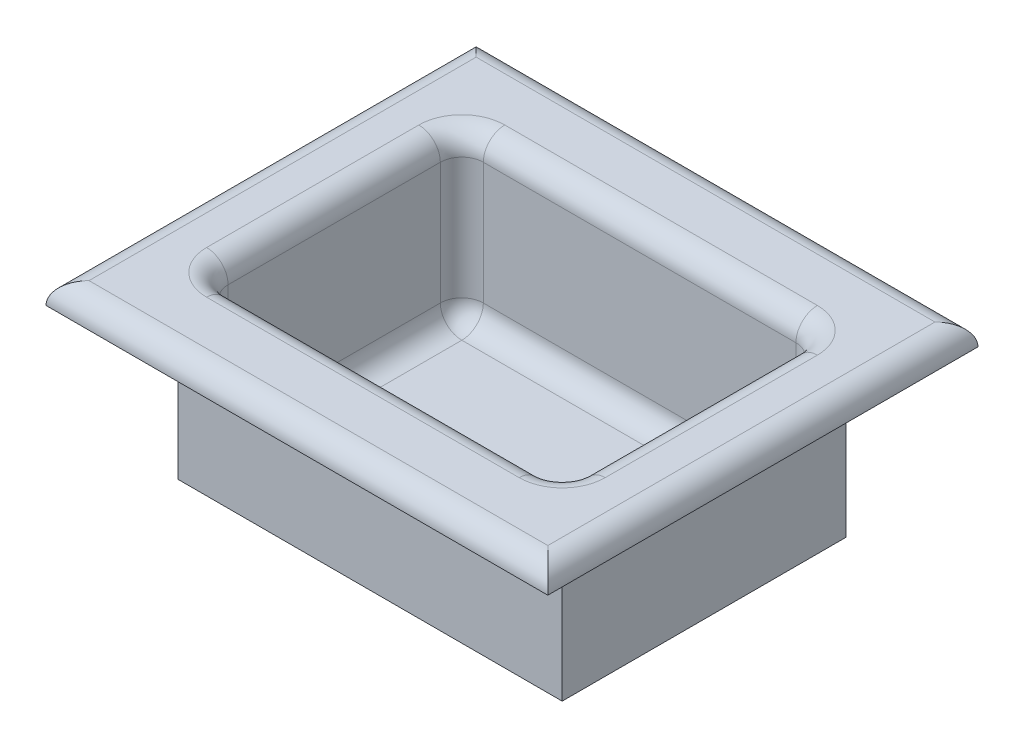
SolidWorks part; units mm, degrees
ref_plane "Спереди" through (0, 0, 0) normal (0, 0, 1) x (1, 0, 0)
ref_plane "Сверху" through (0, 0, 0) normal (0, 1, 0) x (1, 0, 0)
ref_plane "Справа" through (0, 0, 0) normal (1, 0, 0) x (0, 0, -1)
sketch "Sketch1" plane through (0, 0, 0) normal (0, 1, 0) x (1, 0, 0)
  line L1 (26.8, -19.8) -> (-26.8, -19.8)
  line L2 (26.8, -19.8) -> (26.8, 19.8)
  line L3 (26.8, 19.8) -> (-26.8, 19.8)
  line L4 (-26.8, -19.8) -> (-26.8, 19.8)
  line L5 (26.8, -19.8) -> (-26.8, 19.8) construction
  line L6 (26.8, 19.8) -> (-26.8, -19.8) construction
  point P0 (0, 0)
  dimension "D1" = 53.6
  dimension "D2" = 39.6
extrude "Boss-Extrude1" add sketch "Sketch1" along normal blind 2
sketch "Sketch2" plane through (0, 2, 0) normal (0, 1, 0) x (1, 0, 0)
  line L1 (26.8, -19.8) -> (-26.8, -19.8)
  line L2 (26.8, -19.8) -> (26.8, 19.8)
  line L3 (26.8, 19.8) -> (-26.8, 19.8)
  line L4 (-26.8, -19.8) -> (-26.8, 19.8)
  line L5 (26.8, -19.8) -> (-26.8, 19.8) construction
  line L6 (26.8, 19.8) -> (-26.8, -19.8) construction
  line L7 (24.8, -17.8) -> (-24.8, -17.8)
  line L8 (24.8, -17.8) -> (24.8, 17.8)
  line L9 (24.8, 17.8) -> (-24.8, 17.8)
  line L10 (-24.8, -17.8) -> (-24.8, 17.8)
  line L11 (24.8, -17.8) -> (-24.8, 17.8) construction
  line L12 (24.8, 17.8) -> (-24.8, -17.8) construction
  point P0 (0, 0)
  point P7 (0, 0)
  dimension "D1" = 2
  dimension "D2" = 2
extrude "Boss-Extrude2" add sketch "Sketch2" along normal blind 20
sketch "Sketch3" plane through (0, 22, 0) normal (0, 1, 0) x (1, 0, 0)
  line L1 (24.8, -17.8) -> (-24.8, -17.8)
  line L2 (24.8, -17.8) -> (24.8, 17.8)
  line L3 (24.8, 17.8) -> (-24.8, 17.8)
  line L4 (-24.8, -17.8) -> (-24.8, 17.8)
  line L5 (24.8, -17.8) -> (-24.8, 17.8) construction
  line L6 (24.8, 17.8) -> (-24.8, -17.8) construction
  line L7 (35, -30) -> (-35, -30)
  line L8 (35, -30) -> (35, 30)
  line L9 (35, 30) -> (-35, 30)
  line L10 (-35, -30) -> (-35, 30)
  line L11 (35, -30) -> (-35, 30) construction
  line L12 (35, 30) -> (-35, -30) construction
  point P0 (0, 0)
  point P7 (0, 0)
  dimension "D1" = 70
  dimension "D2" = 60
extrude "Boss-Extrude3" add sketch "Sketch3" along normal blind 3
fillet "Fillet1" radius 3 16 edges at (24.8, 13.5, 17.8) (0, 25, 17.8) (-24.8, 13.5, 17.8) (0, 2, 17.8) (24.8, 13.5, -17.8) (-24.8, 13.5, -17.8) (24.8, 2, 0) (-24.8, 2, 0) (0, 2, -17.8) (24.8, 25, 0) (0, 25, -17.8) (-24.8, 25, 0) (0, 25, 30) (0, 25, -30) (35, 25, 0) (-35, 25, 0)
